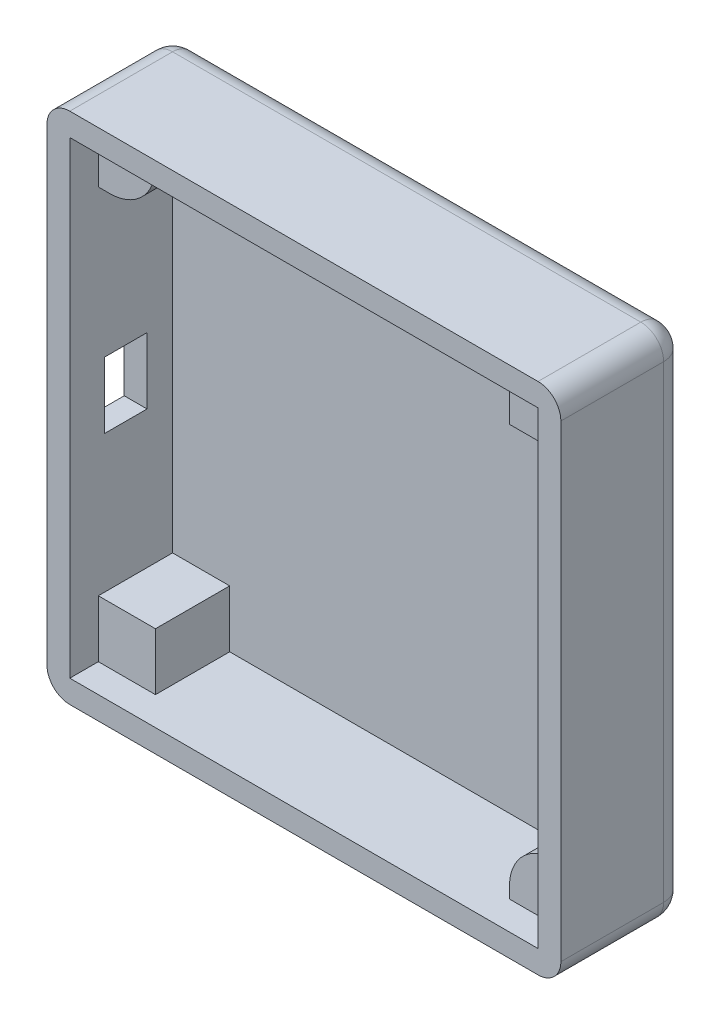
SolidWorks part; units mm, degrees
ref_plane "Piano frontale" through (0, 0, 0) normal (0, 0, 1) x (1, 0, 0)
ref_plane "Piano superiore" through (0, 0, 0) normal (0, 1, 0) x (1, 0, 0)
ref_plane "Piano destro" through (0, 0, 0) normal (1, 0, 0) x (0, 0, -1)
sketch "Schizzo2" plane through (0, 0, 0) normal (0, 0, 1) x (1, 0, 0)
  line L1 (0, 0) -> (45, 0)
  line L2 (0, 0) -> (0, 45)
  line L3 (0, 45) -> (45, 45)
  line L4 (45, 0) -> (45, 45)
  dimension "D1" = 45
  dimension "D2" = 45
extrude "Estrusione-Estrusione2" add sketch "Schizzo2" along normal blind 11
shell "Svuota1" thickness 2 removed face at (22.5, 22.5, 11)
fillet "Raccordo1" radius 2 4 edges at (45, 45, 5.5) (45, 0, 5.5) (0, 0, 5.5) (0, 45, 5.5)
fillet "Raccordo2" radius 2 8 edges at (44.4142, 0.5858, 0) (22.5, 0, 0) (0.5858, 0.5858, 0) (0, 22.5, 0) (0.5858, 44.4142, 0) (22.5, 45, 0) (44.4142, 44.4142, 0) (45, 22.5, 0)
sketch "Schizzo3" plane through (0, 0, 2) normal (0, 0, 1) x (1, 0, 0)
  line L0 (43, 43) -> (2, 43) construction
  line L1 (2, 43) -> (7, 43)
  line L2 (2, 43) -> (2, 38)
  line L3 (2, 38) -> (7, 38)
  line L4 (7, 43) -> (7, 38)
  line L5 (43, 43) -> (2, 43) construction
  dimension "D1" = 5
  dimension "D2" = 5
extrude "Estrusione-Estrusione3" add sketch "Schizzo3" along normal blind 6.5
sketch "Schizzo4" plane through (0, 0, 2) normal (0, 0, 1) x (1, 0, 0)
  line L1 (43, 2) -> (38, 2)
  line L2 (43, 2) -> (43, 7)
  line L3 (43, 7) -> (38, 7)
  line L4 (38, 2) -> (38, 7)
  dimension "D1" = 5
  dimension "D2" = 5
extrude "Estrusione-Estrusione4" add sketch "Schizzo4" along normal blind 6.5
fillet "Raccordo3" radius 4 2 edges at (38, 7, 5.25) (7, 38, 5.25)
sketch "Schizzo5" plane through (0, 0, 2) normal (0, 0, 1) x (1, 0, 0)
  line L0 (43, 2) -> (43, 43) construction
  line L1 (43, 43) -> (38, 43)
  line L2 (43, 43) -> (43, 38)
  line L3 (43, 38) -> (38, 38)
  line L4 (38, 43) -> (38, 38)
  line L5 (43, 43) -> (7, 43) construction
  line L7 (2, 2) -> (7, 2)
  line L8 (2, 2) -> (2, 7)
  line L9 (2, 7) -> (7, 7)
  line L10 (7, 2) -> (7, 7)
  dimension "D1" = 5
  dimension "D2" = 5
  dimension "D3" = 5
  dimension "D4" = 5
extrude "Estrusione-Estrusione5" add sketch "Schizzo5" along normal blind 6.5 contours L2 L1 L4 L3 | L8 L7 L10 L9
sketch "Schizzo7" plane through (0, 0, 0) normal (-1, 0, 0) x (0, 0, 1)
  line L1 (4.2347, 24.8244) -> (7.9559, 24.8244)
  line L2 (4.2347, 24.8244) -> (4.2347, 19.0329)
  line L3 (4.2347, 19.0329) -> (7.9559, 19.0329)
  line L4 (7.9559, 24.8244) -> (7.9559, 19.0329)
extrude "Taglio-Estrusione1" cut sketch "Schizzo7" against normal blind 3
